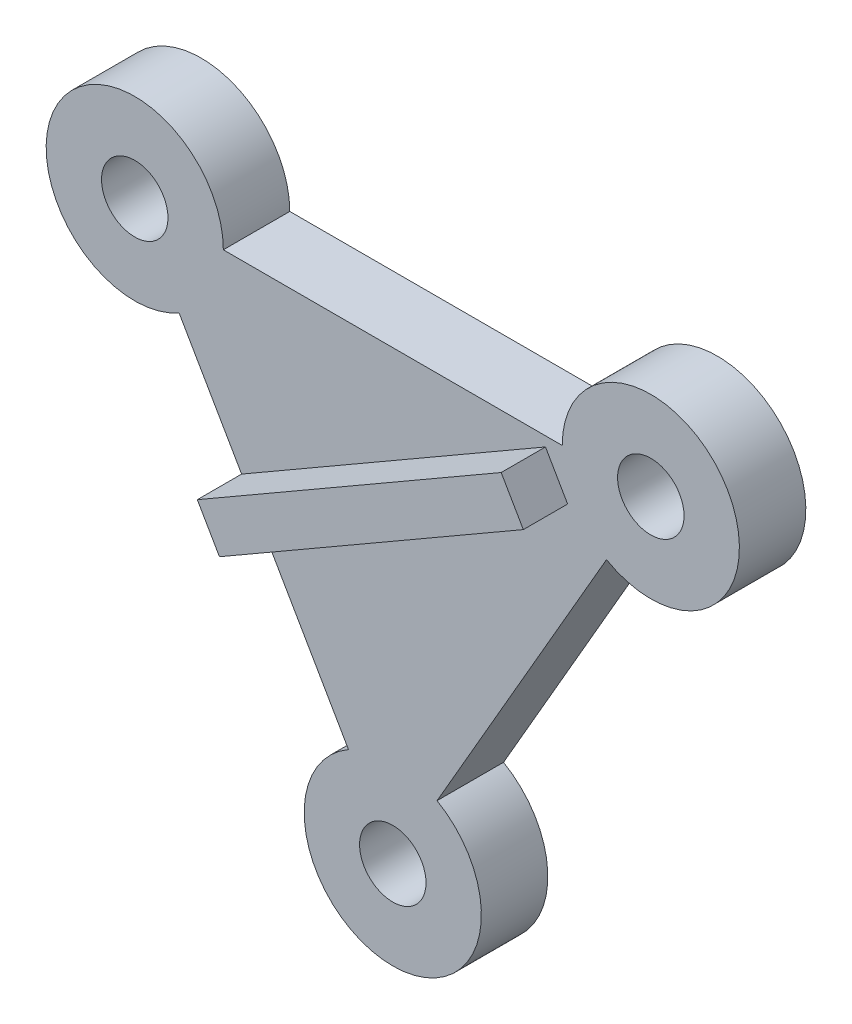
SolidWorks part; units mm, degrees
ref_plane "Ebene vorne" through (0, 0, 0) normal (0, 0, 1) x (1, 0, 0)
ref_plane "Ebene oben" through (0, 0, 0) normal (0, 1, 0) x (1, 0, 0)
ref_plane "Ebene rechts" through (0, 0, 0) normal (1, 0, 0) x (0, 0, -1)
sketch "body" plane through (0, 0, 0) normal (0, 0, 1) x (1, 0, 0)
  line L0 (-17.783, 30.8265) -> (-6.133, 10.6481) construction
  line L1 (5.517, 30.8265) -> (-17.783, 30.8265) construction
  line L2 (-6.133, 10.6481) -> (5.517, 30.8265) construction
  line L3 (-6.133, 30.8265) -> (-6.133, 10.6481) construction
  line L5 (-13.783, 30.8265) -> (1.517, 30.8265)
  line L6 (-15.783, 27.3624) -> (-8.133, 14.1122)
  line L7 (3.517, 27.3624) -> (-4.133, 14.1122)
  arc A1 (-13.783, 30.8265) -> (-15.783, 27.3624) centre (-17.783, 30.8265) ccw
  arc A2 (1.517, 30.8265) -> (3.517, 27.3624) centre (5.517, 30.8265) cw
  arc A3 (-4.133, 14.1122) -> (-8.133, 14.1122) centre (-6.133, 10.6481) cw
  circle A4 centre (-17.783, 30.8265) radius 1.5
  circle A5 centre (5.517, 30.8265) radius 1.5
  circle A6 centre (-6.133, 10.6481) radius 1.5
  dimension "D2" = 4
  dimension "D3" = 3
  dimension "D1" = 23.3
extrude "main-body" add sketch "body" along normal blind 3
ref_axis "Achse1" through (-17.783, 30.8265, 3) along (0, 0, -1)
ref_axis "Achse2" through (-6.133, 10.6481, 3) along (0, 0, -1)
sketch "Skizze3" plane through (0, 0, 3) normal (0, 0, 1) x (1, 0, 0)
  line L0 (-11.958, 20.7373) -> (5.517, 30.8265) construction
  line L1 (-15.783, 27.3624) -> (-8.133, 14.1122) construction
  line L2 (-12.958, 22.4694) -> (4.517, 32.5585) construction
  line L3 (-11.958, 20.7373) -> (-12.958, 22.4694)
  line L4 (-12.958, 22.4694) -> (0.7609, 30.39)
  line L5 (0.7609, 30.39) -> (1.7609, 28.6579)
  line L6 (1.7609, 28.6579) -> (-11.958, 20.7373)
  dimension "D1" = 2
extrude "fit" add sketch "Skizze3" along normal blind 2
